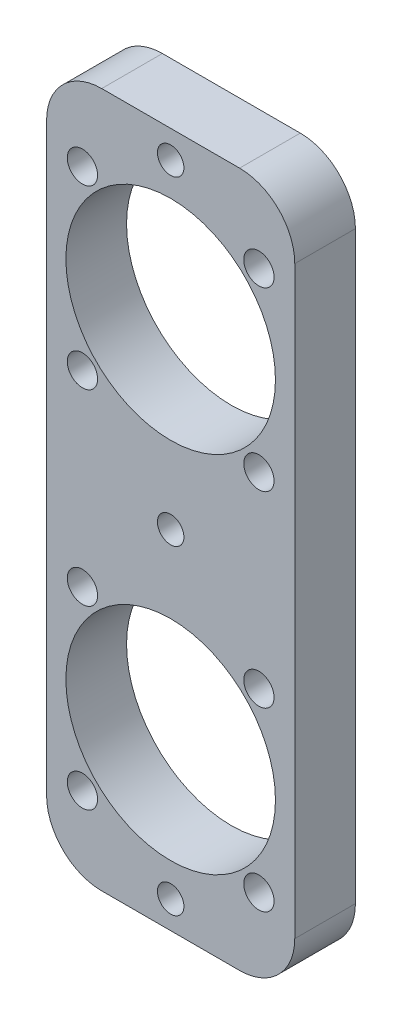
SolidWorks part; units mm, degrees
material "ABS"
ref_plane "X-Y Datum" through (0, 0, 0) normal (0, 0, 1) x (1, 0, 0)
ref_plane "X-Z Datum" through (0, 0, 0) normal (0, 1, 0) x (1, 0, 0)
ref_plane "Y-Z Datum" through (0, 0, 0) normal (1, 0, 0) x (0, 0, -1)
sketch "Sketch1" plane through (0, 0, 0) normal (0, 0, 1) x (1, 0, 0)
  line L0 (0, 30) -> (0, 20) construction
  line L1 (-22.5, 0) -> (22.5, 0) construction
  line L5 (-22.5, -30) -> (22.5, -30)
  line L6 (-22.5, -30) -> (-22.5, 30)
  line L7 (-22.5, 30) -> (22.5, 30)
  line L8 (22.5, -30) -> (22.5, 30)
  line L9 (-22.5, -30) -> (22.5, 30) construction
  line L10 (-22.5, 30) -> (22.5, -30) construction
  line L12 (-22.5, 20) -> (22.5, 20) construction
  circle A0 centre (0, 25) radius 2 construction
  circle A1 centre (0, -25) radius 2 construction
  point P2 (0, 0)
  dimension "D3" = 4
  dimension "D1" = 45
  dimension "D2" = 60
  dimension "D4" = 5
extrude "Boss-Extrude1" add sketch "Sketch1" against normal blind 11 contours L5 L8 L7 L6 A0 A1 region at (0, 0, 0)
sketch "Sketch6" plane through (0, 0, 0) normal (0, 0, 1) x (1, 0, 0)
  circle A0 centre (-16, 16) radius 2.75
  circle A1 centre (16, 16) radius 2.75
  circle A2 centre (16, -16) radius 2.75
  circle A3 centre (-16, -16) radius 2.75
  point P0 (-16, 16)
  point P1 (16, 16)
  point P3 (16, -16)
  point P5 (-16, -16)
  dimension "D1" = 5.5
extrude "Cut-Extrude2" cut sketch "Sketch6" against normal blind 8.5
sketch "Sketch7" plane through (0, 0, 0) normal (0, 0, 1) x (1, 0, 0)
  arc A0 (-19, 0) -> (19, 0) centre (0, 0) ccw construction
  arc A1 (-19, 0) -> (19, 0) centre (0, 0) ccw
  circle A2 centre (0, 0) radius 19
extrude "Cut-Extrude3" cut sketch "Sketch7" against normal through all contours A1 A2 region at (0, 0, 0)
sketch "Sketch11" plane through (0, -30, 0) normal (0, -1, 0) x (1, 0, 0)
  line L4 (-22.5, 0) -> (-22.5, -11)
  line L5 (-22.5, -11) -> (22.5, -11)
  line L6 (22.5, -11) -> (22.5, 0)
  line L7 (22.5, 0) -> (-22.5, 0)
  line L8 (-22.5, 0) -> (-22.5, -11)
  line L9 (-22.5, -11) -> (22.5, -11)
  line L10 (22.5, -11) -> (22.5, 0)
  line L11 (22.5, 0) -> (-22.5, 0)
  dimension "D1" = 0
extrude "Boss-Extrude2" add sketch "Sketch11" along normal blind 6
ref_plane "Plane1" through (0, -33, 0) normal (0, -1, 0) x (-1, 0, 0)
mirror "Mirror1" about plane through (0, -33, 0) normal (0, -1, 0) of "Cut-Extrude3", "Cut-Extrude2", "Boss-Extrude1"
sketch "Sketch12" plane through (0, 0, 0) normal (0, 0, 1) x (1, 0, 0)
  line L0 (0, -96) -> (0, -30)
  line L1 (-22.5, -96) -> (22.5, -96) construction
  line L2 (-22.5, -30) -> (22.5, -30) construction
  line L4 (-22.5, -30) -> (22.5, -30)
  line L5 (22.5, -30) -> (22.5, 30)
  line L6 (22.5, 30) -> (-22.5, 30)
  line L7 (-22.5, 30) -> (-22.5, -30)
  line L8 (-22.5, -30) -> (22.5, -30)
  line L9 (22.5, -30) -> (22.5, 30)
  line L10 (22.5, 30) -> (-22.5, 30)
  line L11 (-22.5, 30) -> (-22.5, -30)
  circle A0 centre (0, -33) radius 2
  circle A1 centre (0, -91) radius 2
  dimension "D2" = 4
  dimension "D4" = 3
  dimension "D3" = 5
  dimension "D1" = 0
hole_wizard "M4 Clearance Hole2" positions "Sketch15" profile "Sketch14" hole size "M4" standard "ANSI Metric" end condition through all
sketch "Sketch15" plane through (0, 0, 0) normal (0, 0, 1) x (1, 0, 0)
  point P0 (0, -91)
  point P3 (0, -33)
  point P6 (0, 25)
sketch "Sketch14" plane through (0, -91, 0) normal (1, 0, 0) x (0, -1, 0)
  line L0 (0, 0) -> (0, 11)
  line L1 (0, 11) -> (2.4, 11)
  line L2 (2.4, 11) -> (2.4, 0)
  line L5 (2.4, 0) -> (0, 0)
  line L11 (0, -6.35) -> (0, 107.95) construction
  dimension "Thru Hole Dia." = 4.8
  dimension "Thru Hole Depth" = 11
fillet "Fillet1" radius 10 4 edges at (-22.5, -96, -5.5) (22.5, -96, -5.5) (22.5, 30, -5.5) (-22.5, 30, -5.5)
